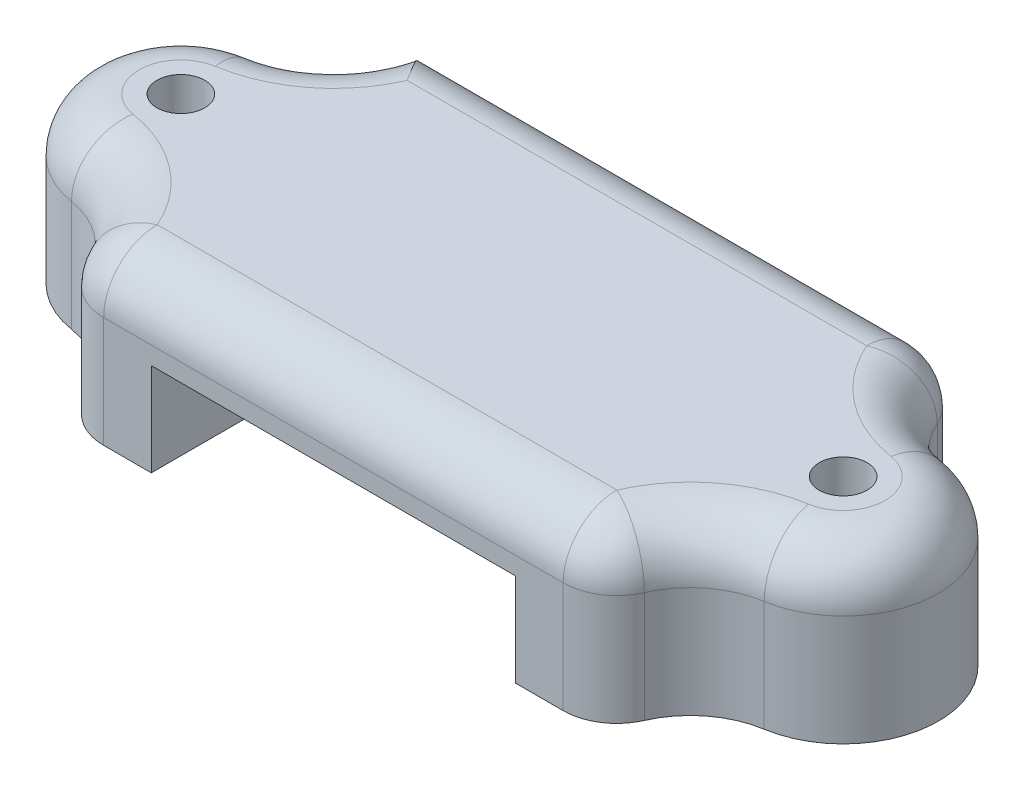
SolidWorks part; units mm, degrees
ref_plane "Front Plane" through (0, 0, 0) normal (0, 0, 1) x (1, 0, 0)
ref_plane "Top Plane" through (0, 0, 0) normal (0, 1, 0) x (1, 0, 0)
ref_plane "Right Plane" through (0, 0, 0) normal (1, 0, 0) x (0, 0, -1)
sketch "Sketch1" plane through (0, 0, 0) normal (0, 1, 0) x (1, 0, 0)
  line L0 (-12.954, 0) -> (12.954, 0) construction
  line L18 (12.954, 0) -> (19.304, 0)
  line L19 (12.954, 0) -> (12.954, 25.4)
  line L20 (12.954, 25.4) -> (19.304, 25.4)
  line L21 (19.304, 0) -> (19.304, 25.4)
  line L22 (-12.954, 0) -> (-19.304, 0)
  line L23 (-12.954, 0) -> (-12.954, 25.4)
  line L24 (-12.954, 25.4) -> (-19.304, 25.4)
  line L25 (-19.304, 0) -> (-19.304, 25.4)
  point P3 (0, 0)
  dimension "D3" = 25.4
  dimension "D1" = 25.908
  dimension "D2" = 6.35
extrude "Boss-Extrude1" add sketch "Sketch1" along normal blind 6.604
sketch "Sketch2" plane through (0, 6.604, 0) normal (0, 1, 0) x (1, 0, 0)
  line L1 (-19.304, 25.4) -> (19.304, 25.4)
  line L2 (-19.304, 25.4) -> (-19.304, 0)
  line L3 (-19.304, 0) -> (19.304, 0)
  line L4 (19.304, 25.4) -> (19.304, 0)
extrude "Boss-Extrude2" add sketch "Sketch2" along normal blind 5.08
sketch "Sketch3" plane through (0, 6.604, 0) normal (0, -1, 0) x (1, 0, 0)
  line L0 (12.954, -25.4) -> (-12.954, -25.4) construction
  line L1 (-6.985, -19.05) -> (6.985, -19.05)
  line L2 (-6.985, -19.05) -> (-6.985, -25.4)
  line L3 (-6.985, -25.4) -> (6.985, -25.4)
  line L4 (6.985, -19.05) -> (6.985, -25.4)
  line L5 (-6.985, -19.05) -> (6.985, -25.4) construction
  line L6 (-6.985, -25.4) -> (6.985, -19.05) construction
  point P0 (0, -22.225)
  dimension "D1" = 13.97
  dimension "D2" = 6.35
extrude "Boss-Extrude3" add sketch "Sketch3" along normal blind 6.604
sketch "Sketch4" plane through (0, 0, -19.05) normal (0, 0, 1) x (1, 0, 0)
  line L0 (-3.81, 3.302) -> (3.81, 3.302) construction
  line L1 (6.985, 0) -> (-6.985, 0) construction
  circle A0 centre (3.81, 3.302) radius 2.159
  circle A1 centre (-3.81, 3.302) radius 2.159
  point P3 (0, 3.302)
  dimension "D1" = 4.318
  dimension "D2" = 4.318
  dimension "D3" = 7.62
  dimension "D4" = 3.302
extrude "Cut-Extrude1" cut sketch "Sketch4" against normal blind 2.54
sketch "Sketch5" plane through (0, 11.684, 0) normal (0, 1, 0) x (1, 0, 0)
  line L0 (-23.5535, 12.7) -> (23.5535, 12.7) construction
  line L1 (-23.5535, 14.4018) -> (23.5535, 14.4018) construction
  line L2 (-23.5535, 19.4818) -> (23.5535, 19.4818) construction
  line L4 (0, 0) -> (0, 25.4) construction
  line L5 (19.304, 25.4) -> (-19.304, 25.4) construction
  line L6 (-19.304, 17.9853) -> (-19.304, 7.4147)
  line L7 (-19.304, 25.4) -> (-19.304, 0) construction
  line L8 (19.304, 17.9853) -> (19.304, 7.4147)
  line L9 (19.304, 0) -> (19.304, 25.4) construction
  arc A0 (-19.304, 17.9853) -> (-19.304, 7.4147) centre (-23.5535, 12.7) ccw
  arc A1 (19.304, 7.4147) -> (19.304, 17.9853) centre (23.5535, 12.7) ccw
  circle A2 centre (23.5535, 12.7) radius 1.7018
  circle A3 centre (-23.5535, 12.7) radius 1.7018
  point P3 (0, 12.7)
  point P23 (0, 12.7)
  dimension "D1" = 3.4036
  dimension "D2" = 5.08
  dimension "D3" = 10.5706
extrude "Boss-Extrude4" add sketch "Sketch5" against normal up to surface (11.684 mm away) up to face at (-16.129, 0, -12.7)
fillet "Fillet1" radius 6.35 4 edges at (-19.304, 5.842, -7.4147) (-19.304, 5.842, -17.9853) (19.304, 5.842, -7.4147) (19.304, 5.842, -17.9853)
fillet "Fillet2" radius 3.81 11 edges at (20.9, 11.684, -21.4477) (30.3353, 11.684, -12.7) (20.9, 11.684, -3.9523) (0, 11.684, 0) (-20.9, 11.684, -3.9523) (-30.3353, 11.684, -12.7) (-20.9, 11.684, -21.4477) (0, 11.684, -25.4) (19.304, 5.842, -25.4) (19.304, 5.842, 0) (-19.304, 5.842, 0)
fillet "Fillet3" radius 1.27 1 edges at (0, 6.604, -19.05)
